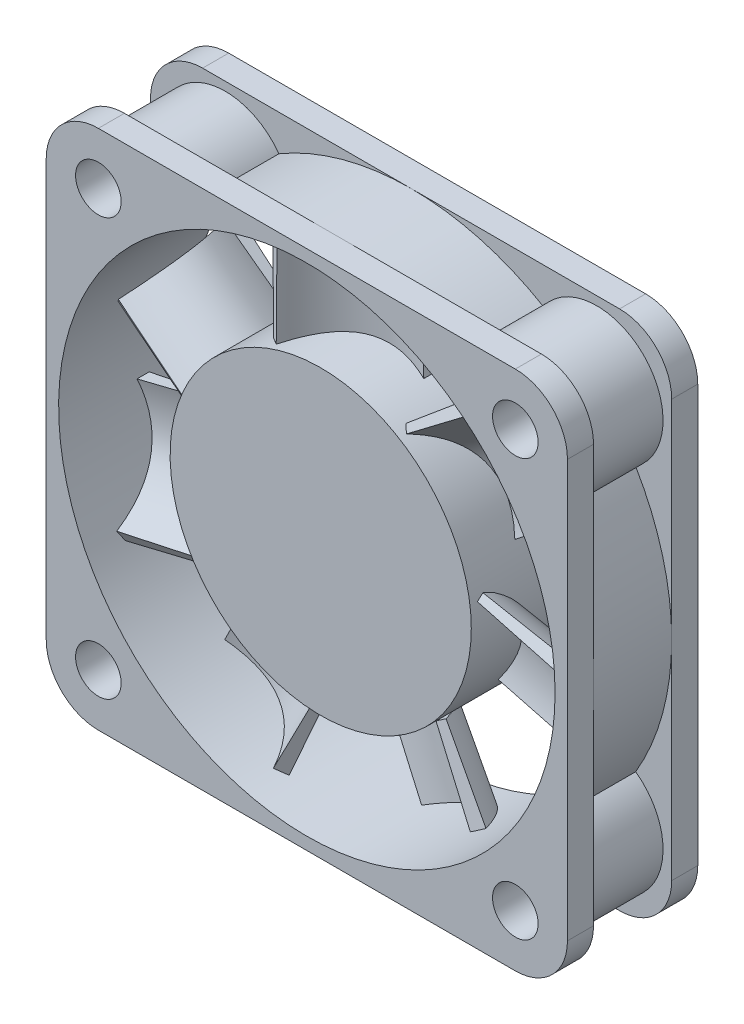
SolidWorks part; units mm, degrees
ref_plane "Front Plane" through (0, 0, 0) normal (0, 0, 1) x (1, 0, 0)
ref_plane "Top Plane" through (0, 0, 0) normal (0, 1, 0) x (1, 0, 0)
ref_plane "Right Plane" through (0, 0, 0) normal (1, 0, 0) x (0, 0, -1)
sketch "Sketch1" plane through (0, 0, 0) normal (0, 1, 0) x (1, 0, 0)
  line L0 (4.6912, 0) -> (4.6912, 0.5969)
  line L1 (-3.2577, -3.3756) -> (-3.7676, -3.0652)
  line L2 (-8.5221, 0) -> (11.1184, 0) construction
  line L3 (-1.6292, 2.8991) -> (1.9509, -3.4715) construction
  arc A0 (-3.2577, -3.3756) -> (4.6912, 0) centre (2.3456, -5.5235) cw
  arc A1 (4.6912, 0.5969) -> (-3.7676, -3.0652) centre (2.2289, -5.3159) ccw
  point P11 (0, 0)
  point P13 (-0.3158, 0.5619)
  dimension "D3" = 9.2175
  dimension "D1" = 8.636
  dimension "D2" = 58.67
  dimension "D4" = 0.5969
  dimension "D5" = 0.5969
  dimension "D7" = 29.335
ref_plane "Plane1" through (4.6912, 0, 0) normal (1, 0, 0) x (0, 0, -1)
sketch "Sketch2" plane through (4.6912, 0, 0) normal (1, 0, 0) x (0, 0, -1)
  line L0 (0, 0) -> (0.5969, 0) construction
  line L1 (0, 0) -> (0.5969, 0)
  line L2 (0.5969, 0) -> (0.7645, 6.5638)
  line L3 (0.7645, 6.5638) -> (-0.1676, 6.5638)
  line L4 (-0.1676, 6.5638) -> (0, 0)
  line L5 (0.2984, 0) -> (0.2984, 6.5638) construction
  dimension "D1" = 0.9322
  dimension "D2" = 6.5659
ref_plane "Plane2" through (0, 0, 0) normal (-0.8718, 0, 0.4899) x (0.4899, 0, 0.8718)
sketch "Sketch4" plane through (0, 0, 0) normal (-0.8718, 0, 0.4899) x (0.4899, 0, 0.8718)
  line L0 (-0.6445, 0) -> (0, 0)
  line L1 (0, 0) -> (0.1438, 6.5643)
  line L2 (0.1438, 6.5643) -> (-0.7884, 6.5643)
  line L3 (-0.7884, 6.5643) -> (-0.6445, 0)
  line L4 (-0.3223, 6.5643) -> (-0.3223, 0) construction
  point P0 (-0.6445, 0)
  point P2 (0, 0)
  dimension "D1" = 6.5659
  dimension "D2" = 0.9322
ref_plane "Plane3" through (-2.38, 0, 3.9099) normal (0.52, 0, -0.8542) x (-0.8542, 0, -0.52)
sketch "Sketch5" plane through (-2.38, 0, 3.9099) normal (0.52, 0, -0.8542) x (-0.8542, 0, -0.52)
  line L0 (1.0275, 0) -> (1.6244, 0) construction
  line L1 (1.0275, 0) -> (1.6244, 0)
  line L2 (1.0275, 0) -> (0.8599, 6.5638)
  line L3 (0.8599, 6.5638) -> (1.7921, 6.5638)
  line L4 (1.7921, 6.5638) -> (1.6244, 0)
  line L5 (1.326, 0) -> (1.326, 6.5638) construction
  dimension "D1" = 0.9322
  dimension "D2" = 6.5659
loft "Loft2" add profiles "Sketch5", "Sketch4", "Sketch2" start constraint default end constraint default connector at (-3.9108, 6.5638, 2.9781) connector at (-0.3862, 6.5643, -0.6873) connector at (4.6912, 6.5638, -0.7645)
sketch "Sketch7" plane through (0, 0, 0) normal (0, 0, 1) x (1, 0, 0)
  circle A0 centre (0.7167, -10.8521) radius 11.557
  dimension "D1" = 23.114
extrude "Boss-Extrude1" add sketch "Sketch7" along normal mid plane 7.874
pattern_circular "CirPattern1" count 7 over 360 about axis through (0.7167, -10.8521, 3.937) along (0, 0, -1) of "Loft2"
sketch "Sketch9" plane through (0, 0, 0) normal (0, 0, 1) x (1, 0, 0)
  line L0 (0.7167, 8.1979) -> (-7.62, -2.8481)
  line L1 (-19.2833, -30.8521) -> (20.7167, -30.8521)
  line L2 (-19.2833, -30.8521) -> (-19.2833, 9.1479)
  line L3 (-19.2833, 9.1479) -> (20.7167, 9.1479)
  line L4 (20.7167, -30.8521) -> (20.7167, 9.1479)
  line L5 (-19.2833, -30.8521) -> (20.7167, 9.1479) construction
  line L6 (-19.2833, 9.1479) -> (20.7167, -30.8521) construction
  line L7 (3.1452, 8.0425) -> (-2.8083, 0.1542)
  line L8 (15.8657, -22.4025) -> (12.011, -13.3025)
  line L9 (17.2145, -20.3771) -> (11.8167, -7.6342)
  line L10 (-16.8607, -18.1963) -> (-7.0525, -19.408)
  line L11 (-15.781, -20.3771) -> (-2.0465, -22.0739)
  arc A0 (-15.781, -20.3771) -> (15.8657, -22.4025) centre (0.7167, -10.8521) ccw
  circle A1 centre (0.7167, -10.8521) radius 11.557 construction
  arc A2 (-7.62, -2.8481) -> (-7.0525, -19.408) centre (0.7167, -10.8521) ccw
  arc A3 (11.8167, -7.6342) -> (-2.8083, 0.1542) centre (0.7167, -10.8521) ccw
  arc A4 (-2.0465, -22.0739) -> (12.011, -13.3025) centre (0.7167, -10.8521) ccw
  arc A5 (0.7167, 8.1979) -> (-16.8607, -18.1963) centre (0.7167, -10.8521) ccw
  arc A6 (17.2145, -20.3771) -> (3.1452, 8.0425) centre (0.7167, -10.8521) ccw
  point P0 (0.7167, -10.8521)
  point P25 (0.7167, -10.8521)
  dimension "D3" = 38.1
  dimension "D1" = 40
  dimension "D2" = 40
  dimension "D4" = 2.032
  dimension "D5" = 7.62
  dimension "D6" = 3
extrude "Boss-Extrude2" add sketch "Sketch9" along normal blind 2 from offset 5 offset against normal yes
sketch "Sketch10" plane through (0, 0, -3) normal (0, 0, 1) x (1, 0, 0)
  line L0 (20.7167, 9.1479) -> (-19.2833, 9.1479) construction
  line L1 (20.7167, 9.1479) -> (-19.2833, -30.8521) construction
  circle A0 centre (0.7167, -10.8521) radius 19.05
  arc A1 (-16.5205, -0.7092) -> (-16.5205, -20.9949) centre (0.7167, -10.8521) ccw
  arc A2 (17.2145, -20.3771) -> (3.1452, 8.0425) centre (0.7167, -10.8521) ccw construction
  arc A3 (10.8596, 6.3852) -> (17.954, -0.7092) centre (14.973, 3.4041) cw
  arc A4 (17.954, -20.9949) -> (10.8596, -28.0893) centre (14.973, -25.1083) cw
  arc A5 (-9.4261, -28.0893) -> (-16.5205, -20.9949) centre (-13.5395, -25.1083) cw
  arc A6 (-16.5205, -0.7092) -> (-9.4261, 6.3852) centre (-13.5395, 3.4041) cw
  arc A7 (10.8596, 6.3852) -> (-9.4261, 6.3852) centre (0.7167, -10.8521) ccw
  arc A8 (17.954, -20.9949) -> (17.954, -0.7092) centre (0.7167, -10.8521) ccw
  arc A9 (-9.4261, -28.0893) -> (10.8596, -28.0893) centre (0.7167, -10.8521) ccw
  point P28 (0.7167, -10.8521)
  dimension "D1" = 5.08
  dimension "D2" = 10.033
  dimension "D3" = 4
extrude "Boss-Extrude5" add sketch "Sketch10" along normal blind 6
sketch "Sketch11" plane through (0, 0, 3) normal (0, 0, 1) x (1, 0, 0)
  line L1 (-19.2833, -30.8521) -> (20.7167, -30.8521)
  line L2 (-19.2833, -30.8521) -> (-19.2833, 9.1479)
  line L3 (-19.2833, 9.1479) -> (20.7167, 9.1479)
  line L4 (20.7167, -30.8521) -> (20.7167, 9.1479)
  line L5 (-19.2833, -30.8521) -> (20.7167, 9.1479) construction
  line L6 (-19.2833, 9.1479) -> (20.7167, -30.8521) construction
  circle A0 centre (0.7167, -10.8521) radius 19.05 construction
  circle A1 centre (0.7167, -10.8521) radius 19.05
  point P0 (0.7167, -10.8521)
extrude "Boss-Extrude6" add sketch "Sketch11" along normal blind 2
sketch "Sketch12" plane through (0, 0, 5) normal (0, 0, 1) x (1, 0, 0)
  line L1 (-15.2833, -26.8521) -> (16.7167, -26.8521) construction
  line L2 (-15.2833, -26.8521) -> (-15.2833, 5.1479) construction
  line L3 (-15.2833, 5.1479) -> (16.7167, 5.1479) construction
  line L4 (16.7167, -26.8521) -> (16.7167, 5.1479) construction
  line L5 (-15.2833, -26.8521) -> (16.7167, 5.1479) construction
  line L6 (-15.2833, 5.1479) -> (16.7167, -26.8521) construction
  circle A0 centre (-15.2833, 5.1479) radius 1.75
  circle A1 centre (16.7167, 5.1479) radius 1.75
  circle A2 centre (16.7167, -26.8521) radius 1.75
  circle A3 centre (-15.2833, -26.8521) radius 1.75
  point P0 (0.7167, -10.8521)
  dimension "D2" = 3.5
  dimension "D1" = 32
extrude "Cut-Extrude1" cut sketch "Sketch12" against normal through all
fillet "Fillet1" radius 4 8 edges at (20.7167, -30.8521, 4) (20.7167, -30.8521, -4) (-19.2833, -30.8521, -4) (-19.2833, -30.8521, 4) (-19.2833, 9.1479, 4) (-19.2833, 9.1479, -4) (20.7167, 9.1479, -4) (20.7167, 9.1479, 4)
sketch "Sketch13" plane through (0, 0, -5) normal (0, 0, -1) x (-1, 0, 0)
  line L0 (-0.7167, -10.8521) -> (-0.7167, -22.4091) construction
  line L1 (-0.7167, -19.8254) -> (0.5533, -19.8254) construction
  line L2 (-0.7167, -19.8254) -> (-1.9867, -19.8254) construction
  arc A0 (-12.011, -13.3025) -> (2.0465, -22.0739) centre (-0.7167, -10.8521) ccw construction
  point P1 (0.5533, -19.8254)
  point P12 (-1.9867, -19.8254)
  dimension "D1" = 1.27
  dimension "D2" = 1.27
  dimension "D3" = 2.5837
sketch "0_0_Point" plane through (0, 0, -5) normal (0, 0, -1) x (-1, 0, 0)
  point P0 (-1.9867, -19.8254)
other "0_0" parameters "Diameter"=2, "StubLength"=2
ref_axis "Axis1" through (1.9867, -19.8254, -15) along (0, 0, 1)
sketch "0_1_Point" plane through (0, 0, -5) normal (0, 0, -1) x (-1, 0, 0)
  point P0 (0.5533, -19.8254)
other "0_1" parameters "Diameter"=2, "StubLength"=2
ref_axis "Axis2" through (-0.5533, -19.8254, -15) along (0, 0, 1)
